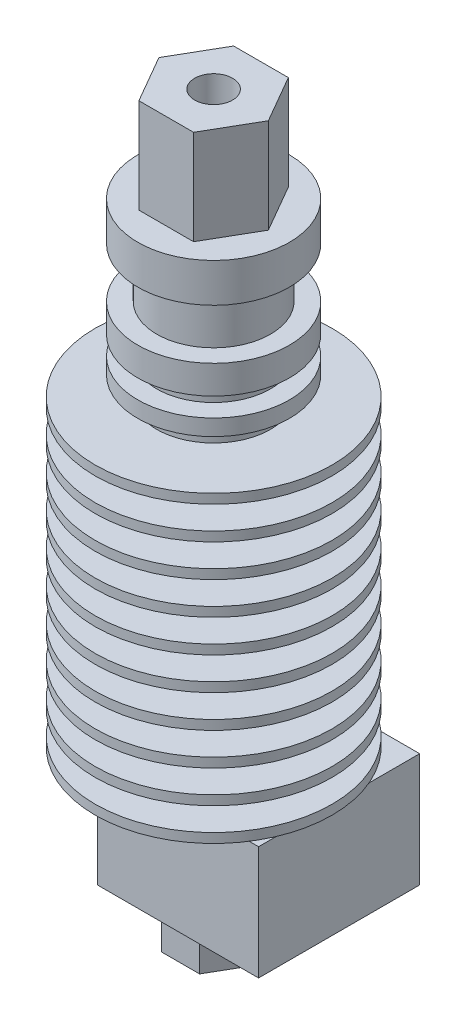
SolidWorks part; units mm, degrees
material "6061 Alloy"
ref_plane "Front Plane" through (0, 0, 0) normal (0, 0, 1) x (1, 0, 0)
ref_plane "Top Plane" through (0, 0, 0) normal (0, 1, 0) x (1, 0, 0)
ref_plane "Right Plane" through (0, 0, 0) normal (1, 0, 0) x (0, 0, -1)
sketch "Sketch1" plane through (0, 0, 0) normal (0, 0, 1) x (1, 0, 0)
  line L0 (0, 0) -> (0, 61.158) construction
  line L1 (1, 0) -> (12.5, 0)
  line L2 (12.5, 0) -> (12.5, 1)
  line L3 (12.5, 1) -> (8, 1)
  line L4 (8, 1) -> (8, 3.4444)
  line L5 (8, 3.4444) -> (12.5, 3.4444)
  line L6 (12.5, 3.4444) -> (12.5, 4.4444)
  line L7 (12.5, 4.4444) -> (8, 4.4444)
  line L8 (8, 4.4444) -> (8, 6.8889)
  line L9 (8, 6.8889) -> (12.5, 6.8889)
  line L10 (12.5, 6.8889) -> (12.5, 7.8889)
  line L11 (12.5, 7.8889) -> (8, 7.8889)
  line L12 (8, 7.8889) -> (8, 10.3333)
  line L13 (8, 10.3333) -> (12.5, 10.3333)
  line L14 (12.5, 10.3333) -> (12.5, 11.3333)
  line L15 (12.5, 11.3333) -> (8, 11.3333)
  line L16 (8, 11.3333) -> (8, 13.7778)
  line L17 (8, 13.7778) -> (12.5, 13.7778)
  line L18 (12.5, 13.7778) -> (12.5, 14.7778)
  line L19 (12.5, 14.7778) -> (8, 14.7778)
  line L20 (8, 14.7778) -> (8, 17.2222)
  line L21 (8, 17.2222) -> (12.5, 17.2222)
  line L22 (12.5, 17.2222) -> (12.5, 18.2222)
  line L23 (12.5, 18.2222) -> (8, 18.2222)
  line L24 (8, 18.2222) -> (8, 20.6667)
  line L25 (8, 20.6667) -> (12.5, 20.6667)
  line L26 (12.5, 20.6667) -> (12.5, 21.6667)
  line L27 (12.5, 21.6667) -> (8, 21.6667)
  line L28 (8, 21.6667) -> (8, 24.1111)
  line L29 (8, 24.1111) -> (12.5, 24.1111)
  line L30 (12.5, 24.1111) -> (12.5, 25.1111)
  line L31 (12.5, 25.1111) -> (8, 25.1111)
  line L32 (8, 25.1111) -> (8, 27.5556)
  line L33 (8, 27.5556) -> (12.5, 27.5556)
  line L34 (12.5, 27.5556) -> (12.5, 28.5556)
  line L35 (12.5, 28.5556) -> (8, 28.5556)
  line L36 (8, 28.5556) -> (8, 31)
  line L37 (8, 31) -> (12.5, 31)
  line L38 (12.5, 31) -> (12.5, 32)
  line L39 (12.5, 32) -> (6, 32)
  line L41 (6, 32) -> (6, 34)
  line L42 (6, 34) -> (8, 34)
  line L43 (8, 34) -> (8, 35.7)
  line L44 (8, 35.7) -> (6, 35.7)
  line L45 (6, 35.7) -> (6, 37.7)
  line L46 (6, 37.7) -> (8, 37.7)
  line L47 (8, 37.7) -> (8, 40.7)
  line L48 (8, 40.7) -> (6, 40.7)
  line L49 (6, 40.7) -> (6, 46)
  line L50 (6, 46) -> (8, 46)
  line L51 (8, 46) -> (8, 50.1)
  line L52 (8, 50.1) -> (1, 50.1)
  line L54 (1, 50.1) -> (1, 0)
  dimension "D1" = 32
  dimension "D2" = 1
  dimension "D3" = 12.5
  dimension "D4" = 1
  dimension "D5" = 7
  dimension "D6" = 8
  dimension "D7" = 6
  dimension "D8" = 14
  dimension "D9" = 4.1
  dimension "D10" = 3
  dimension "D11" = 5.3
  dimension "D12" = 2
  dimension "D13" = 2
revolve "Revolve1" add sketch "Sketch1" angle 360 about L0
sketch "Sketch2" plane through (0, 0, 0) normal (0, -1, 0) x (1, 0, 0)
  circle A0 centre (0, 0) radius 1.7927
  circle A1 centre (0, 0) radius 1 construction
  circle A2 centre (0, 0) radius 1
extrude "Boss-Extrude1" add sketch "Sketch2" along normal blind 3
sketch "Sketch3" plane through (0, -3, 0) normal (0, -1, 0) x (1, 0, 0)
  line L1 (-8.5, -13.2422) -> (8.5, -13.2422)
  line L2 (-8.5, -13.2422) -> (-8.5, 3.7578)
  line L3 (-8.5, 3.7578) -> (8.5, 3.7578)
  line L4 (8.5, -13.2422) -> (8.5, 3.7578)
  circle A0 centre (0, 0) radius 1 construction
  circle A1 centre (0, 0) radius 1
  point P7 (0, 3.7578)
  dimension "D1" = 17
extrude "Boss-Extrude2" add sketch "Sketch3" along normal blind 12 separate body
sketch "Sketch4" plane through (0, -15, 0) normal (0, -1, 0) x (1, 0, 0)
  line L1 (2.0207, 3.5) -> (-2.0207, 3.5)
  line L2 (-2.0207, 3.5) -> (-4.0415, 0)
  line L3 (-4.0415, 0) -> (-2.0207, -3.5)
  line L4 (-2.0207, -3.5) -> (2.0207, -3.5)
  line L5 (2.0207, -3.5) -> (4.0415, 0)
  line L6 (4.0415, 0) -> (2.0207, 3.5)
  circle A0 centre (0, 0) radius 3.5 construction
  circle A1 centre (0, 0) radius 1 construction
  circle A2 centre (0, 0) radius 1
  dimension "D1" = 7
extrude "Boss-Extrude3" add sketch "Sketch4" along normal blind 3
sketch "Sketch5" plane through (0, 0, 0) normal (0, 0, 1) x (1, 0, 0)
  line L0 (0, 0) -> (0, -22.864) construction
  line L1 (0.2, -18) -> (0.2, -20)
  line L2 (2.0207, -18) -> (-2.0207, -18) construction
  line L3 (0.2, -20) -> (2.9453, -18)
  line L4 (4.0415, -18) -> (2.0207, -18) construction
  line L5 (2.9453, -18) -> (0.2, -18)
  dimension "D1" = 2
  dimension "D2" = 0.2
revolve "Revolve2" add sketch "Sketch5" angle 360 about L0
sketch "Sketch6" plane through (8.5, 0, 0) normal (1, 0, 0) x (0, 0, -1)
  circle A0 centre (7.4507, -8.9214) radius 2.5
  circle A1 centre (10.5916, -13.2255) radius 0.7357
  dimension "D1" = 5
extrude "Cut-Extrude1" [suppressed] cut sketch "Sketch6" against normal through all
sketch "Sketch8" plane through (0, 50.1, 0) normal (0, 1, 0) x (1, 0, 0)
  line L1 (2.8868, 5) -> (-2.8868, 5)
  line L2 (-2.8868, 5) -> (-5.7735, 0)
  line L3 (-5.7735, 0) -> (-2.8868, -5)
  line L4 (-2.8868, -5) -> (2.8868, -5)
  line L5 (2.8868, -5) -> (5.7735, 0)
  line L6 (5.7735, 0) -> (2.8868, 5)
  circle A0 centre (0, 0) radius 5 construction
  circle A1 centre (0, 0) radius 2
  dimension "D2" = 4
  dimension "D1" = 10
extrude "Boss-Extrude4" add sketch "Sketch8" along normal blind 10
sketch "Sketch9" [suppressed] plane through (8.5, 0, 0) normal (1, 0, 0) x (0, 0, -1)
  circle A0 centre (7.4507, -8.9214) radius 2.5 construction
  circle A1 centre (7.4507, -8.9214) radius 2.5
extrude "Boss-Extrude5" [suppressed] add sketch "Sketch9" along normal blind 4 and the other way blind 15
ref_plane "Plane1" through (0, 0, -7.2422) normal (0, 0, -1) x (-1, 0, 0)
ref_point "Ponto2"
